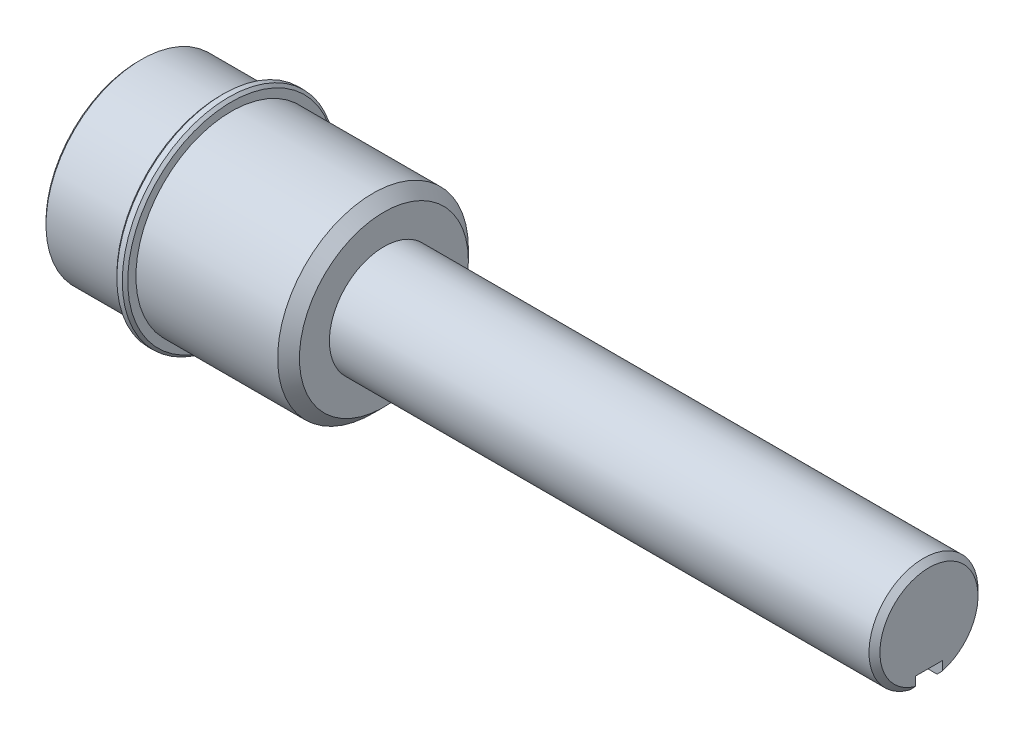
SolidWorks part; units mm, degrees
ref_plane "前视基准面" through (0, 0, 0) normal (0, 0, 1) x (1, 0, 0)
ref_plane "上视基准面" through (0, 0, 0) normal (0, 1, 0) x (1, 0, 0)
ref_plane "右视基准面" through (0, 0, 0) normal (1, 0, 0) x (0, 0, -1)
other "Configuration Table"
sketch "草图1" plane through (0, 0, 0) normal (0, 0, 1) x (1, 0, 0)
  line L0 (0, 0) -> (0, 17.5)
  line L1 (0, 17.5) -> (15, 17.5)
  line L2 (15, 17.5) -> (15, 19.5)
  line L3 (15, 19.5) -> (17, 19.5)
  line L4 (17, 19.5) -> (17, 17.5)
  line L5 (17, 17.5) -> (45, 17.5)
  line L6 (45, 17.5) -> (45, 10)
  line L7 (45, 10) -> (145, 10)
  line L8 (145, 10) -> (145, 0)
  line L9 (145, 0) -> (0, 0)
  line L10 (0, 0) -> (-21.734, 0) construction
  dimension "D1" = 35
  dimension "D2" = 39
  dimension "D3" = 20
  dimension "D4" = 28
  dimension "D5" = 2
  dimension "D6" = 45
  dimension "D7" = 100
revolve "旋转1" add sketch "草图1" angle 360 about L10
chamfer "倒角1" distance 2 angle 45 1 edges at (45, 0, -17.5)
chamfer "倒角3" distance 0.5 angle 45 3 edges at (17, 0, -19.5) (15, 0, -19.5) (0, 0, -17.5)
hole_wizard "M6 螺纹孔的螺纹孔钻头1" positions "草图2" profile "草图3" hole size "M6" standard "GB"
sketch "草图2" plane through (0, 0, 0) normal (-1, 0, 0) x (0, 0, 1)
  point P0 (0, 0)
sketch "草图3" plane through (0, 0, 0) normal (0, 1, 0) x (0, 0, 1)
  line L0 (0, 0) -> (0, 19.5022)
  line L1 (0, 19.5022) -> (2.5, 18)
  line L2 (2.5, 18) -> (2.5, 0)
  line L5 (2.5, 0) -> (0, 0)
  line L10 (0, 19.5022) -> (-2.5, 18) construction
  line L11 (0, -6.35) -> (0, 107.95) construction
  dimension "孔直径" = 5
  dimension "孔深度" = 18
  dimension "导头角度" = 118
chamfer "倒角2" distance 1 angle 45 2 edges at (145, 0, -10) (0, 0, 2.5)
ref_plane "基准面1" through (0, -13.5, 0) normal (0, 1, 0) x (1, 0, 0)
sketch "草图5" plane through (0, -13.5, 0) normal (0, 1, 0) x (1, 0, 0)
  line L0 (0, 4) -> (11, 4)
  line L1 (0, 17) -> (0, -17) construction
  line L2 (11, -4) -> (0, -4)
  line L3 (0, -4) -> (0, 4)
  line L4 (15, 17.5) -> (15, -17.5) construction
  arc A0 (11, 4) -> (11, -4) centre (11, 0) cw
  dimension "D1" = 11
extrude "切除-拉伸2" cut sketch "草图5" against normal blind 10
sketch "草图6" plane through (0, 0, 0) normal (0, 1, 0) x (1, 0, 0)
  line L0 (145, -2.5) -> (131, -2.5)
  line L1 (145, -9) -> (145, 9) construction
  line L2 (131, 2.5) -> (145, 2.5)
  line L3 (145, 2.5) -> (145, -2.5)
  arc A0 (131, -2.5) -> (131, 2.5) centre (131, 0) cw
  point P9 (145, 0)
  dimension "D1" = 5
  dimension "D2" = 14
extrude "切除-拉伸3" cut sketch "草图6" against normal blind 10 from offset 7 offset against normal yes
sketch "草图7" plane through (0, 0, 0) normal (0, 1, 0) x (1, 0, 0)
  line L0 (48, 0) -> (62, 0) construction
  line L1 (48, 3) -> (62, 3)
  line L2 (48, -3) -> (62, -3)
  line L3 (45, -15.5) -> (45, 15.5) construction
  arc A0 (48, 3) -> (48, -3) centre (48, 0) ccw
  arc A1 (62, -3) -> (62, 3) centre (62, 0) ccw
  point P2 (55, 0)
  dimension "D1" = 6
  dimension "D2" = 14
extrude "切除-拉伸4" cut sketch "草图7" against normal blind 10 from offset 6.5 offset against normal yes
